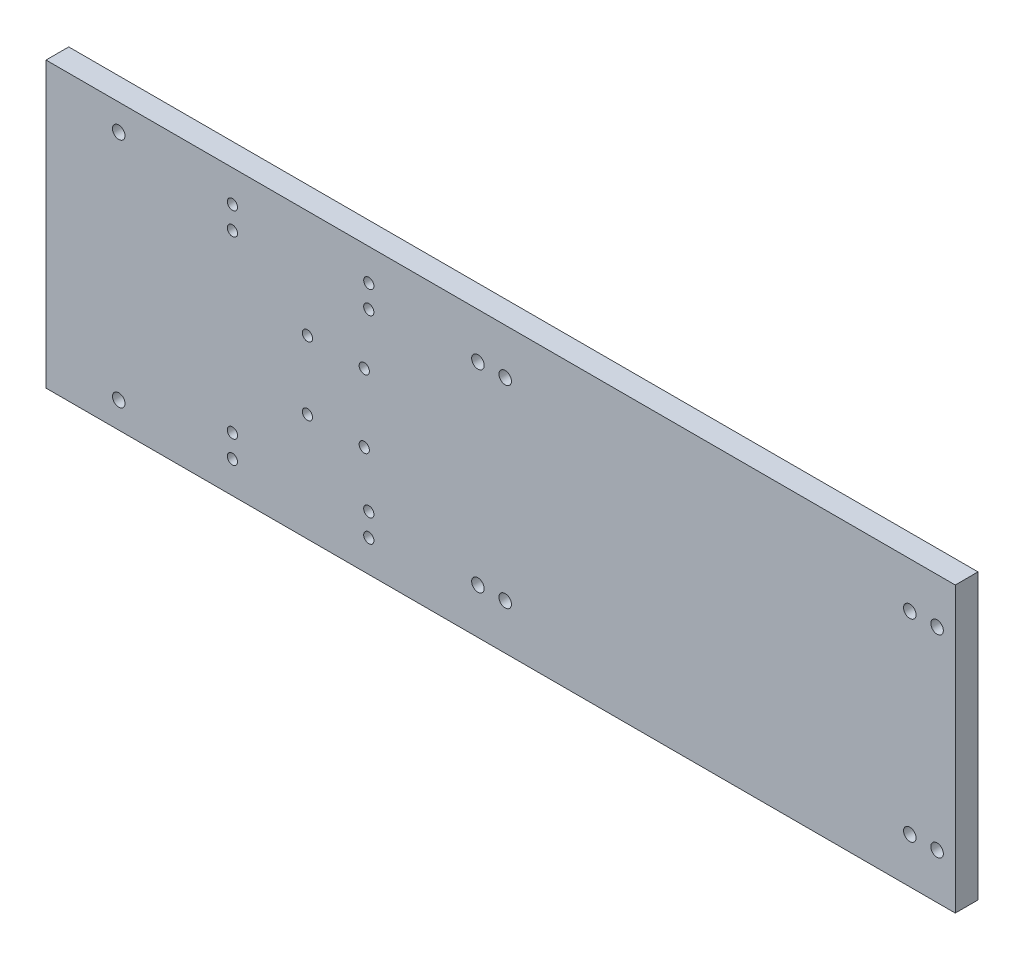
SolidWorks part; units mm, degrees
ref_plane "Front Plane" through (0, 0, 0) normal (0, 0, 1) x (1, 0, 0)
ref_plane "Top Plane" through (0, 0, 0) normal (0, 1, 0) x (1, 0, 0)
ref_plane "Right Plane" through (0, 0, 0) normal (1, 0, 0) x (0, 0, -1)
sketch "Sketch1" plane through (0, 0, 0) normal (0, 0, 1) x (1, 0, 0)
  line L0 (-60, 15) -> (-85, 15) construction
  line L1 (-200, -62.5) -> (200, -62.5)
  line L2 (-200, -62.5) -> (-200, 62.5)
  line L3 (-200, 62.5) -> (200, 62.5)
  line L4 (200, -62.5) -> (200, 62.5)
  line L5 (-200, -62.5) -> (200, 62.5) construction
  line L6 (-200, 62.5) -> (200, -62.5) construction
  line L7 (-85, 15) -> (-85, -15) construction
  line L8 (-85, -15) -> (-60, -15) construction
  line L9 (-60, -15) -> (-60, 15) construction
  line L10 (2, 42.5) -> (-10, 42.5) construction
  line L11 (-10, 42.5) -> (-10, -42.5) construction
  line L12 (-10, -42.5) -> (2, -42.5) construction
  line L13 (2, -42.5) -> (2, 42.5) construction
  line L14 (192, 42.5) -> (180, 42.5) construction
  line L15 (180, 42.5) -> (180, -42.5) construction
  line L16 (180, -42.5) -> (192, -42.5) construction
  line L17 (192, -42.5) -> (192, 42.5) construction
  line L18 (-168, 51) -> (-168, -51) construction
  line L19 (180, 0) -> (2, 0) construction
  line L20 (-60, 0) -> (-10, 0) construction
  line L21 (-58, 38.5) -> (-118, 38.5) construction
  line L22 (-118, 38.5) -> (-118, -38.5) construction
  line L23 (-118, -38.5) -> (-58, -38.5) construction
  line L24 (-58, -38.5) -> (-58, 38.5) construction
  line L25 (-168, 0) -> (-118, 0) construction
  line L26 (-58, 38.5) -> (-58, 48.5) construction
  line L27 (-58, 48.5) -> (-118, 48.5) construction
  line L28 (-118, 48.5) -> (-118, 38.5) construction
  line L29 (-58, -38.5) -> (-58, -48.5) construction
  line L30 (-58, -48.5) -> (-118, -48.5) construction
  line L31 (-118, -48.5) -> (-118, -38.5) construction
  point P0 (-60, 15)
  point P5 (-168, -51)
  point P6 (192, 42.5)
  point P7 (180, 42.5)
  point P9 (192, -42.5)
  point P10 (180, -42.5)
  point P11 (2, 42.5)
  point P13 (2, -42.5)
  point P14 (-10, -42.5)
  point P15 (-85, 15)
  point P19 (-85, -15)
  point P20 (-60, -15)
  point P21 (-168, 51)
  point P25 (0, 0)
  point P43 (-58, 38.5)
  point P44 (-118, 38.5)
  point P45 (-118, -38.5)
  point P46 (-58, -38.5)
  point P55 (-10, 42.5)
  point P57 (-58, 48.5)
  point P58 (-118, 48.5)
  point P59 (-58, -48.5)
  point P60 (-118, -48.5)
  dimension "D3" = 85
  dimension "D4" = 12
  dimension "D5" = 12
  dimension "D6" = 50
  dimension "D8" = 77
  dimension "D9" = 60
  dimension "D11" = 102
  dimension "D12" = 178
  dimension "D13" = 25
  dimension "D14" = 8
  dimension "D15" = 10
  dimension "D16" = 10
  dimension "D19" = 125
  dimension "D20" = 400
  dimension "D21" = 32
  dimension "D7" = 30
  dimension "D10" = 50
extrude "Boss-Extrude1" add sketch "Sketch1" along normal blind 10
hole_wizard "Taladro de margen para M51" positions "Croquis7" profile "Croquis6" hole size "M5" standard "IS" end condition through all
sketch "Croquis7" plane through (0, 0, 0) normal (0, 0, -1) x (-1, 0, 0)
  point P0 (-192, 42.5)
  point P3 (-180, 42.5)
  point P6 (-192, -42.5)
  point P9 (-180, -42.5)
  point P12 (-2, 42.5)
  point P15 (10, 42.5)
  point P18 (-2, -42.5)
  point P21 (10, -42.5)
  point P24 (168, 51)
  point P27 (168, -51)
sketch "Croquis6" plane through (192, 42.5, 0) normal (1, 0, 0) x (0, 1, 0)
  line L0 (0, 0) -> (0, 10)
  line L1 (0, 10) -> (2.75, 10)
  line L2 (2.75, 10) -> (2.75, 0)
  line L5 (2.75, 0) -> (0, 0)
  line L11 (0, -6.35) -> (0, 107.95) construction
  dimension "Diámetro de taladro hasta el siguiente" = 5.5
  dimension "Profundidad de taladro hasta el siguiente" = 10
hole_wizard "Taladro de margen para M41" positions "Croquis8" profile "Croquis9" hole size "M4" standard "IS" end condition through all
sketch "Croquis8" plane through (0, 0, 0) normal (0, 0, -1) x (-1, 0, 0)
  point P0 (58, 38.5)
  point P3 (118, 38.5)
  point P6 (118, -38.5)
  point P9 (58, -38.5)
  point P12 (60, -15)
  point P15 (85, -15)
  point P18 (85, 15)
  point P21 (60, 15)
  point P24 (58, -48.5)
  point P27 (118, -48.5)
  point P30 (58, 48.5)
  point P33 (118, 48.5)
sketch "Croquis9" plane through (-58, 38.5, 0) normal (1, 0, 0) x (0, 1, 0)
  line L0 (0, 0) -> (0, 10)
  line L1 (0, 10) -> (2.25, 10)
  line L2 (2.25, 10) -> (2.25, 0)
  line L5 (2.25, 0) -> (0, 0)
  line L11 (0, -6.35) -> (0, 107.95) construction
  dimension "Diámetro de taladro hasta el siguiente" = 4.5
  dimension "Profundidad de taladro hasta el siguiente" = 10
